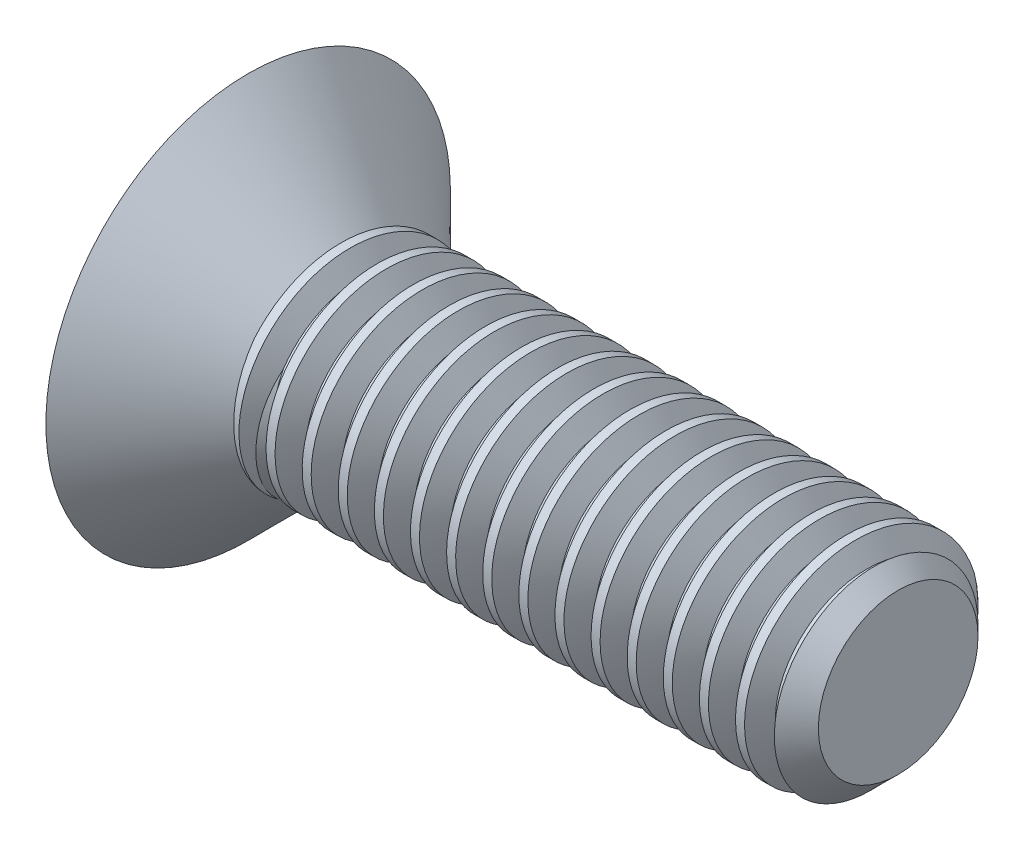
SolidWorks part; units mm, degrees
material "AISI 304"
ref_plane "Front Plane" through (0, 0, 0) normal (0, 0, 1) x (1, 0, 0)
ref_plane "Top Plane" through (0, 0, 0) normal (0, 1, 0) x (1, 0, 0)
ref_plane "Right Plane" through (0, 0, 0) normal (1, 0, 0) x (0, 0, -1)
sketch "Sketch1" plane through (0, 0, 0) normal (0, 0, 1) x (1, 0, 0)
  line L0 (0, 0) -> (0, 2.8)
  line L1 (0, 2.8) -> (1.3, 1.5)
  line L2 (1.3, 1.5) -> (9, 1.5)
  line L3 (9, 1.5) -> (9, 0)
  line L4 (9, 0) -> (0, 0)
  line L5 (0, 0) -> (-45.4653, 0) construction
  dimension "D1" = 5.6
  dimension "D2" = 3
  dimension "D3" = 9
  dimension "D4" = 45
revolve "Revolve1" add sketch "Sketch1" angle 360 about L5
chamfer "Chamfer1" distance 0.395 angle 45 1 edges at (9, 1.5, 0)
sketch "Sketch2" plane through (9, 0, 0) normal (1, 0, 0) x (0, 0, -1)
  circle A0 centre (0, 0) radius 1.5 construction
  circle A1 centre (0, 0) radius 1.5
curve "Helix/Spiral1" pitch 0.5 height 9 radius 1.5 left hand yes centre (9, 0, 0) axis (-1, 0, 0) start towards (0, 0, 1)
sketch "Sketch3" plane through (0, 0, 0) normal (0, 0, 1) x (1, 0, 0)
  line L4 (8.9375, 1.6083) -> (9.4375, 1.6083) construction
  line L5 (9.4375, 1.6083) -> (9.1875, 1.1752) construction
  line L6 (9.1875, 1.1752) -> (8.9375, 1.6083) construction
  line L7 (9, 1.5) -> (9.375, 1.5) construction
  line L8 (8.605, 1.5) -> (1.3, 1.5) construction
  line L9 (8.9688, 1.5541) -> (9.4062, 1.5541)
  line L10 (9.4062, 1.5541) -> (9.2188, 1.2294)
  line L11 (9.2188, 1.2294) -> (9.1562, 1.2294)
  line L12 (9.1562, 1.2294) -> (8.9688, 1.5541)
  line L13 (9, 1.5) -> (8.9375, 1.6083) construction
  line L14 (9.1875, 1.5541) -> (9.1875, 1.6083) construction
  line L15 (9.1875, 1.2294) -> (9.1875, 1.1752) construction
  dimension "D1" = 0.5
  dimension "D2" = 0.0625
sweep "Cut-Sweep1" cut profiles "Sketch3" path "Helix/Spiral1" align with end faces yes
sketch "Sketch13" plane through (0, 0, 0) normal (-1, 0, 0) x (0, 0, 1)
  circle A0 centre (0, 0) radius 1.5541
  arc A4 (1.4007, -0.6733) -> (0.5058, -1.4695) centre (0, 0) ccw construction
extrude "Boss-Extrude3" add sketch "Sketch13" against normal up to surface (1.2459 mm away) up to face at (1.2716, -0.0584, 0.6088)
sketch "Sketch14" plane through (0, 0, 0) normal (-1, 0, 0) x (0, 0, 1)
  line L0 (0, 0) -> (0, 1.2161)
  line L1 (0, 0) -> (1.2161, 0)
  line L2 (0, 0) -> (0.7021, 0.7021) construction
  line L3 (0.2056, 1.1986) -> (0.2056, 0.7021)
  line L4 (0.2056, 0.7021) -> (0.2056, 0.2056) construction
  line L5 (0.7021, 0.2056) -> (0.2056, 0.2056) construction
  line L6 (1.1986, 0.2056) -> (0.7021, 0.2056)
  line L7 (0.2056, 0.7021) -> (0.3511, 0.3511)
  line L8 (0.3511, 0.3511) -> (0.7021, 0.2056)
  line L9 (0.7021, 0.7021) -> (0.3511, 0.3511) construction
  arc A0 (0, 1.2161) -> (0.2056, 1.1986) centre (0, 0) cw
  arc A1 (1.2161, 0) -> (1.1986, 0.2056) centre (0, 0) ccw
  arc A2 (0.7021, 0.2056) -> (0.2056, 0.7021) centre (0.7021, 0.7021) cw construction
  point P4 (0.3511, 0.3511)
  point P12 (0, 1.2161)
  dimension "D1" = 1.2161
extrude "Cut-Extrude1" cut sketch "Sketch14" against normal blind 0.55
pattern_circular "CirPattern1" count 4 over 360 about axis through (0, 0, 0) along (1, 0, 0) of "Cut-Extrude1"
equation "\"diam_head\"=0.005600"
equation "\"L_head\"=0.001650"
equation "\"countersink_angle\"=90"
equation "\"L\"=0.009000"
equation "\"diam_thread\"=0.003000"
equation "\"pitch\"=0.000500"
equation "\"D1@Sketch1\"=\"diam_head\"*1000"
equation "\"D2@Sketch1\"=\"diam_thread\"*1000"
equation "\"D3@Sketch1\"=\"L\"*1000"
equation "\"D1@Chamfer1\"=\"pitch\"*1000*0.79"
equation "\"D1@Sketch3\"=\"pitch\"*1000"
equation "\"D3@Helix/Spiral1\"=\"L\"*1000"
equation "\"D4@Helix/Spiral1\"=\"pitch\"*1000"
equation "\"D1@Cut-Extrude1\"=\"L_head\"*1000/3"
equation "\"D2@Sketch3\"=\"pitch\"*1000/8"
equation "\"D1@Boss-Extrude3\"=\"L_head\"*1000"
